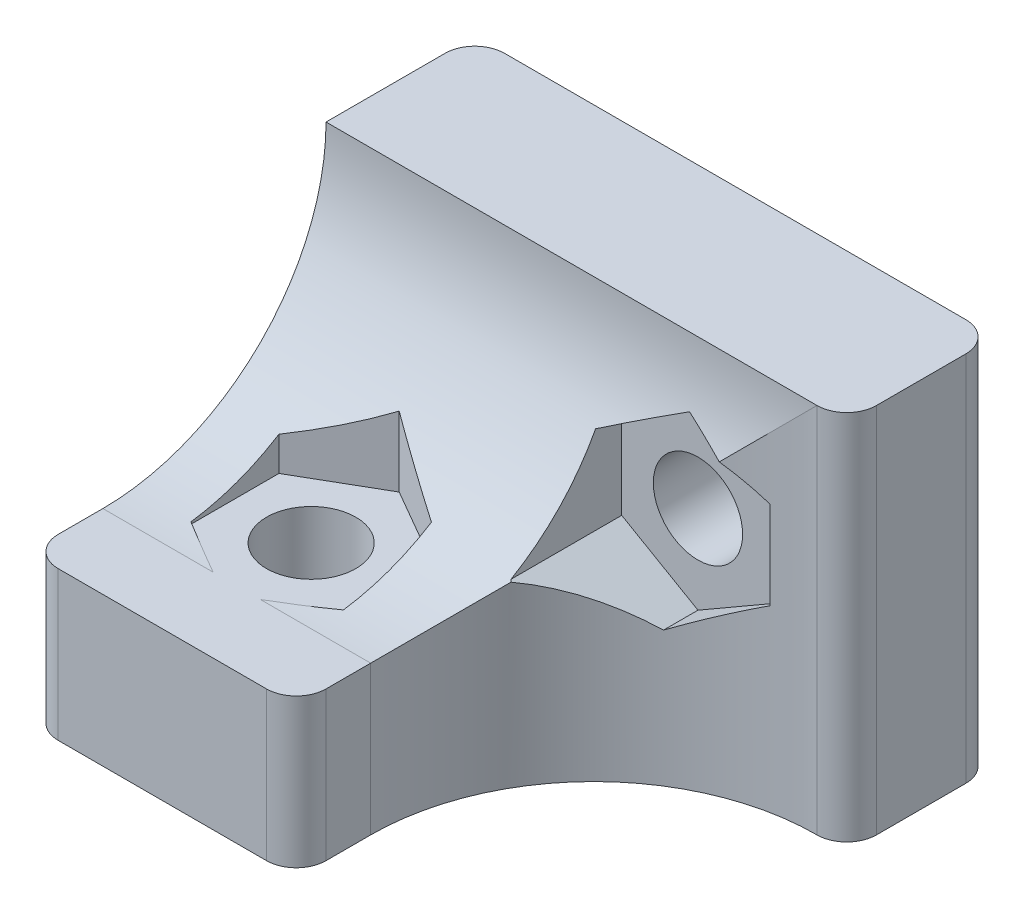
SolidWorks part; units mm, degrees
ref_plane "Front Plane" through (0, 0, 0) normal (0, 0, 1) x (1, 0, 0)
ref_plane "Top Plane" through (0, 0, 0) normal (0, 1, 0) x (1, 0, 0)
ref_plane "Right Plane" through (0, 0, 0) normal (1, 0, 0) x (0, 0, -1)
sketch "Sketch1" plane through (0, 0, 0) normal (0, 0, 1) x (1, 0, 0)
  line L1 (-17.5, 12.5) -> (17.5, 12.5)
  line L2 (-17.5, 12.5) -> (-17.5, -12.5)
  line L3 (-17.5, -12.5) -> (17.5, -12.5)
  line L4 (17.5, 12.5) -> (17.5, -12.5)
  line L5 (-17.5, 12.5) -> (17.5, -12.5) construction
  line L6 (-17.5, -12.5) -> (17.5, 12.5) construction
  point P0 (0, 0)
  dimension "D1" = 25
  dimension "D2" = 35
extrude "Boss-Extrude1" add sketch "Sketch1" along normal blind 10
sketch "Sketch2" plane through (0, 0, 10) normal (0, 0, 1) x (1, 0, 0)
  line L0 (-17.5, -12.5) -> (7.5, -12.5) construction
  line L1 (-17.5, -12.5) -> (17.5, -12.5) construction
  line L2 (7.5, -12.5) -> (7.5, 2.5) construction
  circle A0 centre (7.5, 2.5) radius 3
  dimension "D3" = 6
  dimension "D1" = 25
  dimension "D2" = 15
extrude "Cut-Extrude1" cut sketch "Sketch2" against normal through all
sketch "Sketch3" plane through (0, 0, 10) normal (0, 0, 1) x (1, 0, 0)
  line L1 (0.5, -12.5) -> (-17.5, -12.5)
  line L2 (0.5, -12.5) -> (0.5, -2.5)
  line L3 (0.5, -2.5) -> (-17.5, -2.5)
  line L4 (-17.5, -12.5) -> (-17.5, -2.5)
  point P5 (0, 0)
  dimension "D1" = 18
  dimension "D2" = 10
extrude "Boss-Extrude2" add sketch "Sketch3" along normal blind 20
sketch "Sketch4" plane through (0, -2.5, 0) normal (0, 1, 0) x (1, 0, 0)
  line L0 (-17.5, -10) -> (-8.5, -10) construction
  line L1 (0.5, -10) -> (-17.5, -10) construction
  line L2 (-8.5, -10) -> (-8.5, -20) construction
  circle A0 centre (-8.5, -20) radius 3
  dimension "D3" = 6
  dimension "D1" = 9
  dimension "D2" = 10
extrude "Cut-Extrude2" cut sketch "Sketch4" against normal through all contours A0
fillet "Fillet2" radius 15 2 edges at (-8.5, -2.5, 10) (0.5, -7.5, 10)
fillet "Fillet3" radius 2 5 edges at (17.5, 0, 0) (-17.5, 0, 0) (-17.5, -7.5, 30) (0.5, -7.5, 30) (17.5, 0, 10)
sketch "Sketch5" plane through (0, 0, 0) normal (0, 0, -1) x (-1, 0, 0)
  line L1 (-7.5, -3.4178) -> (-2.375, -0.4589)
  line L2 (-2.375, -0.4589) -> (-2.375, 5.4589)
  line L3 (-2.375, 5.4589) -> (-7.5, 8.4178)
  line L4 (-7.5, 8.4178) -> (-12.625, 5.4589)
  line L5 (-12.625, 5.4589) -> (-12.625, -0.4589)
  line L6 (-12.625, -0.4589) -> (-7.5, -3.4178)
  circle A0 centre (-7.5, 2.5) radius 5.125 construction
sketch "Sketch6" plane through (0, -12.5, 0) normal (0, -1, 0) x (1, 0, 0)
  line L7 (-8.5, 14.0822) -> (-3.375, 17.0411)
  line L8 (-3.375, 17.0411) -> (-3.375, 22.9589)
  line L9 (-3.375, 22.9589) -> (-8.5, 25.9178)
  line L10 (-8.5, 25.9178) -> (-13.625, 22.9589)
  line L11 (-13.625, 22.9589) -> (-13.625, 17.0411)
  line L12 (-13.625, 17.0411) -> (-8.5, 14.0822)
  circle A0 centre (-8.5, 20) radius 5.125 construction
extrude "Cut-Extrude3" cut sketch "Sketch5" against normal through all from offset 10 contours L4 L5 L6 L1 L2 L3 offset against normal yes
extrude "Cut-Extrude4" cut sketch "Sketch6" against normal through all from offset 10 offset against normal yes
